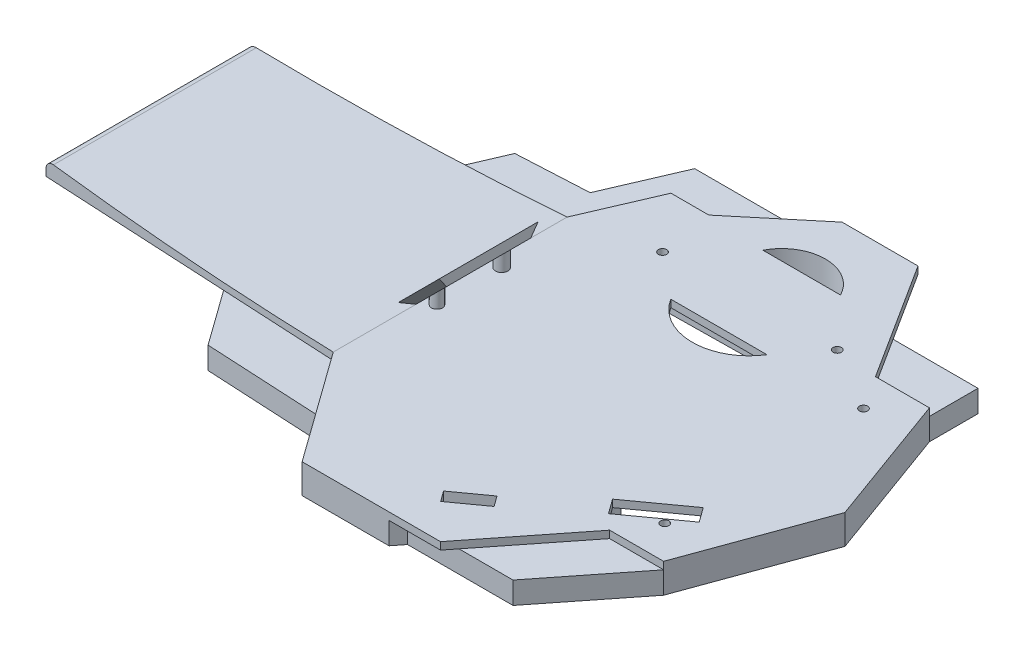
SolidWorks part; units mm, degrees
ref_plane "前视基准面" through (0, 0, 0) normal (0, 0, 1) x (1, 0, 0)
ref_plane "上视基准面" through (0, 0, 0) normal (0, 1, 0) x (1, 0, 0)
ref_plane "右视基准面" through (0, 0, 0) normal (1, 0, 0) x (0, 0, -1)
other "Configuration Table"
sketch "草图2" plane through (0, 0, 0) normal (0, 1, 0) x (1, 0, 0)
  line L0 (0, 0) -> (243.6421, 0) construction
  line L30 (176.8295, 36.1855) -> (82.5273, -31.8251) construction
  line L35 (141.8216, 68.0827) -> (121.1619, 68.0827)
  line L36 (176.8295, 36.1855) -> (190, 0)
  line L37 (104.1466, -61.9173) -> (82.5273, -31.8251)
  line L38 (82.5273, -31.8251) -> (0, -27.5)
  line L39 (0, -27.5) -> (0, 27.5)
  line L40 (0, 27.5) -> (82.5273, 31.8251)
  line L43 (190, 0) -> (176.8295, -36.1855)
  line L45 (82.5273, 31.8251) -> (91.0398, 51.6089)
  line L51 (104.1466, -61.9173) -> (190, 0) construction
  line L53 (141.8216, -61.9173) -> (104.1466, -61.9173)
  line L55 (82.5273, 31.8251) -> (342.4089, 31.8251) construction
  line L57 (176.8295, 36.1855) -> (176.8295, 0) construction
  line L58 (176.8295, 0) -> (176.8295, -36.1855) construction
  line L59 (82.5273, -31.8251) -> (342.4089, -31.8251) construction
  line L62 (91.0398, 51.6089) -> (101.351, 51.6089)
  line L63 (101.351, 51.6089) -> (121.1619, 68.0827)
  line L64 (141.8216, 68.0827) -> (162.1337, 36.1855)
  line L65 (162.1337, 36.1855) -> (176.8295, 36.1855)
  line L66 (176.8295, -36.1855) -> (162.1337, -36.1855)
  line L67 (162.1337, -36.1855) -> (141.8216, -61.9173)
  dimension "D1" = 190
  dimension "D2" = 130
  dimension "D4" = 55
  dimension "D6" = 93
  dimension "D7" = 93
  dimension "D8" = 140
extrude "凸台-拉伸1" add sketch "草图2" along normal blind 2
sketch "草图6" plane through (0, 2, 0) normal (0, 1, 0) x (1, 0, 0)
  line L0 (82.5273, 31.8251) -> (82.5273, -31.8251)
  line L1 (82.5273, -31.8251) -> (0, -27.5)
  line L2 (0, -27.5) -> (0, 27.5)
  line L3 (0, 27.5) -> (82.5273, 31.8251)
extrude "凸台-拉伸2" add sketch "草图6" along normal blind 2
sketch "草图7" plane through (0, 0, 0) normal (0, 0, 1) x (1, 0, 0)
  line L2 (82.5273, 2) -> (82.5273, 30.7408)
  line L3 (82.5273, 30.7408) -> (0, 4)
  spline S0 degree 2 poles (82.5273, 2) (41.2153, 1.0012) (0, 4) knots 0 0 0 1 1 1
extrude "切除-拉伸3" cut sketch "草图7" against normal through all both and the other way through all
fillet "圆角1" radius 2 1 edges at (0, 4, 0)
ref_plane "基准面3" through (0, -12, 0) normal (0, -1, 0) x (-1, 0, 0)
sketch "草图10" plane through (0, 0, 0) normal (0, -1, 0) x (1, 0, 0)
  line L0 (0, 27.5) -> (82.5273, 31.8251)
  line L1 (82.5273, 31.8251) -> (171.8529, 31.8251)
  line L2 (171.8529, 31.8251) -> (171.8529, -31.8251)
  line L3 (171.8529, -31.8251) -> (82.5273, -31.8251)
  line L4 (82.5273, -31.8251) -> (0, -27.5)
  line L5 (0, -27.5) -> (0, 27.5)
sketch "草图12" plane through (0, 2, 0) normal (0, 1, 0) x (1, 0, 0)
  line L0 (176.8295, 36.1855) -> (82.5273, -31.8251)
  line L1 (190, 0) -> (104.1466, -61.9173)
  line L2 (183.4148, 18.0928) -> (93.337, -46.8712) construction
  line L3 (190, 0) -> (176.8295, 36.1855) construction
  line L4 (82.5273, -31.8251) -> (104.1466, -61.9173) construction
sketch "草图13" plane through (0, 0, 0) normal (0, -1, 0) x (1, 0, 0)
  line L0 (53.5015, -30.3039) -> (58.4123, -41.717)
  line L1 (82.5273, -31.8251) -> (0, -27.5) construction
  line L2 (58.4123, -41.717) -> (77.9269, -42.7397)
  line L3 (77.9269, -42.7397) -> (86.4844, -62.6282)
  line L4 (86.4844, -62.6282) -> (136.1647, -62.6282)
  line L5 (176.8295, 36.1855) -> (190, 0)
  line L6 (190, 0) -> (176.8295, -36.1855)
  line L7 (136.1647, -62.6282) -> (144.5841, -49.4069)
  line L8 (144.5841, -49.4069) -> (176.8295, -49.4069)
  line L9 (176.8295, -49.4069) -> (176.8295, -36.1855)
  line L11 (176.8295, 36.1855) -> (158.7432, 59.0976)
  line L12 (158.7432, 59.0976) -> (130.0164, 59.0976)
  line L13 (130.0164, 59.0976) -> (127.7906, 61.9173)
  line L14 (104.1466, 61.9173) -> (141.8216, 61.9173) construction
  line L15 (127.7906, 61.9173) -> (104.1466, 61.9173)
  line L16 (104.1466, 61.9173) -> (93.337, 46.8712)
  line L17 (93.337, 46.8712) -> (61.8459, 45.2208)
  line L18 (61.8459, 45.2208) -> (51.0363, 30.1747)
  line L19 (0, 27.5) -> (82.5273, 31.8251) construction
  line L20 (51.0363, 30.1747) -> (171.8529, 31.8251)
  line L21 (171.8529, 31.8251) -> (171.8529, -31.8251)
  line L22 (171.8529, -31.8251) -> (53.5015, -30.3039)
extrude "凸台-拉伸4" add sketch "草图13" along normal blind 6 contours L18 L20 L21 L22 L0 L2 L3 L4 L7 L8 L9 L6 L5 L11 L12 L13 L15 L16 L17
sketch "草图17" plane through (0, 2, 0) normal (0, 1, 0) x (1, 0, 0)
  line L3 (116.0112, 26.5953) -> (142.1812, 26.5953)
  line L4 (138.1274, 50.6813) -> (116.9896, 50.6813)
  arc A1 (116.0112, 26.5953) -> (142.1812, 26.5953) centre (129.0962, 34.7996) ccw
  arc A2 (116.9896, 50.6813) -> (138.1274, 50.6813) centre (127.5585, 45.2443) cw
sketch "草图18" plane through (0, 2, 0) normal (0, 1, 0) x (1, 0, 0)
  line L4 (169.5639, -18.1259) -> (155.2183, -28.4719)
  line L5 (172.4314, -22.1019) -> (169.5639, -18.1259)
  line L6 (158.0858, -32.4479) -> (172.4314, -22.1019)
  line L7 (155.2183, -28.4719) -> (158.0858, -32.4479)
  line L8 (169.5639, -18.1259) -> (155.2183, -28.4719)
  line L9 (172.4314, -22.1019) -> (169.5639, -18.1259)
  line L10 (158.0858, -32.4479) -> (172.4314, -22.1019)
  line L11 (155.2183, -28.4719) -> (158.0858, -32.4479)
  line L12 (130.3021, -49.5646) -> (132.3616, -52.4203)
  line L13 (132.3616, -52.4203) -> (140.8147, -46.3239)
  line L14 (140.8147, -46.3239) -> (138.7552, -43.4683)
  line L15 (138.7552, -43.4683) -> (130.3021, -49.5646)
  line L16 (130.3021, -49.5646) -> (132.3616, -52.4203)
  line L17 (132.3616, -52.4203) -> (140.8147, -46.3239)
  line L18 (140.8147, -46.3239) -> (138.7552, -43.4683)
  line L19 (138.7552, -43.4683) -> (130.3021, -49.5646)
  dimension "D1" = 0
  dimension "D2" = 0
extrude "切除-拉伸7" cut sketch "草图18" against normal through all
sketch "草图19" plane through (0, 2, 0) normal (0, 1, 0) x (1, 0, 0)
  line L0 (82.5273, -31.8251) -> (176.8295, 36.1855)
  line L1 (176.8295, 36.1855) -> (190, 0)
  line L2 (190, 0) -> (104.1466, -61.9173)
  line L3 (104.1466, -61.9173) -> (82.5273, -31.8251)
ref_plane "基准面4" through (40.2637, -40.2637, 0) normal (-0.7071, 0.7071, 0) x (0, 0, -1)
sketch "草图23" plane through (40.2637, -40.2637, 0) normal (-0.7071, 0.7071, 0) x (0, 0, -1)
  line L0 (-9.292, -59.7699) -> (13.6381, -59.7699)
  line L1 (-31.8251, -59.7699) -> (31.8251, -59.7699) construction
  line L2 (13.6381, -59.7699) -> (13.6381, -71.5206)
  line L3 (13.6381, -71.5206) -> (-9.292, -71.5206)
  line L4 (-9.292, -71.5206) -> (-9.292, -60.8098)
  line L5 (-9.292, -60.8098) -> (-9.292, -59.7699)
  point P7 (0, 0)
extrude "凸台-拉伸5" add sketch "草图23" along normal blind 2 draft 45 separate body draft outward yes
sketch "草图24" plane through (0, 2, 0) normal (0, 1, 0) x (1, 0, 0)
  circle A0 centre (85.4903, 11.0478) radius 1.6973
  circle A1 centre (85.4903, -6.5413) radius 1.5
  point P4 (0, 0)
  point P5 (0, 0)
  point P6 (85.4903, 11.0478)
  point P7 (85.4903, -6.5413)
  point P8 (0, 0)
  point P9 (0, 0)
extrude "凸台-拉伸11" add sketch "草图24" along normal up to surface (2.9629 mm away) separate body contours A0 | A1 region at (85.4903, 2, -11.0478) region at (85.4903, 2, 6.5413) up to face at (86.6818, 6.1545, -2.173)
ref_plane "基准面6" through (0, 4, 0) normal (0, 1, 0) x (1, 0, 0)
sketch "草图25" plane through (0, 4, 0) normal (0, 1, 0) x (1, 0, 0)
  line L1 (67.0613, -53.2409) -> (67.0613, 49.4655) construction
  line L2 (-9.3986, 0) -> (224.1358, 0) construction
  circle A0 centre (67.0613, -25.5664) radius 3
  circle A1 centre (67.0613, 25.5664) radius 3
  circle A2 centre (168.0155, 27.0476) radius 1
  circle A3 centre (168.0155, -27.0476) radius 1
  circle A4 centre (150.7888, 25.9399) radius 3
  circle A5 centre (150.7888, -25.9399) radius 3
  point P11 (168.0155, 27.0476)
  point P14 (168.0155, -27.0476)
extrude "切除-拉伸8" cut sketch "草图17" against normal through all contours L4 A2 | L4 A2 | A1 L3 | A1 L3 region at (129.0962, 2, -23.6319) region at (127.5585, 2, -53.332)
hole_wizard "#4-40 螺纹孔3" positions "草图25" profile "草图26" tap size "#4-40" standard "ANSI Inch" end condition through all
sketch "草图26" plane through (168.0155, 4, 27.0476) normal (1, 0, 0) x (0, 0, 1)
  line L0 (0, 0) -> (0, 10)
  line L1 (0, 10) -> (1.1303, 10)
  line L2 (1.1303, 10) -> (1.1303, 0)
  line L5 (1.1303, 0) -> (0, 0)
  line L11 (0, -6.35) -> (0, 107.95) construction
  dimension "通孔螺纹孔钻头直径" = 2.2606
  dimension "通孔螺纹孔钻头深度" = 10
cosmetic thread "孔螺纹线4" parameters "D2"=2.8448
cosmetic thread "孔螺纹线5" parameters "D2"=2.8448
sketch "草图29" plane through (0, 0, 0) normal (0, -1, 0) x (1, 0, 0)
  circle A0 centre (67.0613, 25.5664) radius 3
  circle A1 centre (67.0613, -25.5664) radius 3
  circle A2 centre (150.7888, 25.9399) radius 3
  circle A3 centre (150.7888, -25.9399) radius 3
extrude "凸台-拉伸14" add sketch "草图29" along normal blind 5 contours A0 | A1 | A2 | A3 region at (67.0613, 0, 25.5664) region at (67.0613, 0, -25.5664) region at (150.7888, 0, 25.9399) region at (150.7888, 0, -25.9399)
sketch "草图33" plane through (0, 2, 0) normal (0, 1, 0) x (1, 0, 0)
  point P0 (150.6182, 37.307)
  point P3 (103.7494, 36.6082)
hole_wizard "#4-40 螺纹孔4" positions "草图33" profile "草图32" tap size "#4-40" standard "ANSI Inch" end condition through all
sketch "草图32" plane through (150.6182, 2, -37.307) normal (1, 0, 0) x (0, 0, 1)
  line L0 (0, 0) -> (0, 8)
  line L1 (0, 8) -> (1.1303, 8)
  line L2 (1.1303, 8) -> (1.1303, 0)
  line L5 (1.1303, 0) -> (0, 0)
  line L11 (0, -6.35) -> (0, 107.95) construction
  dimension "通孔螺纹孔钻头直径" = 2.2606
  dimension "通孔螺纹孔钻头深度" = 8
cosmetic thread "孔螺纹线8" parameters "D2"=2.8448
cosmetic thread "孔螺纹线9" parameters "D2"=2.8448
